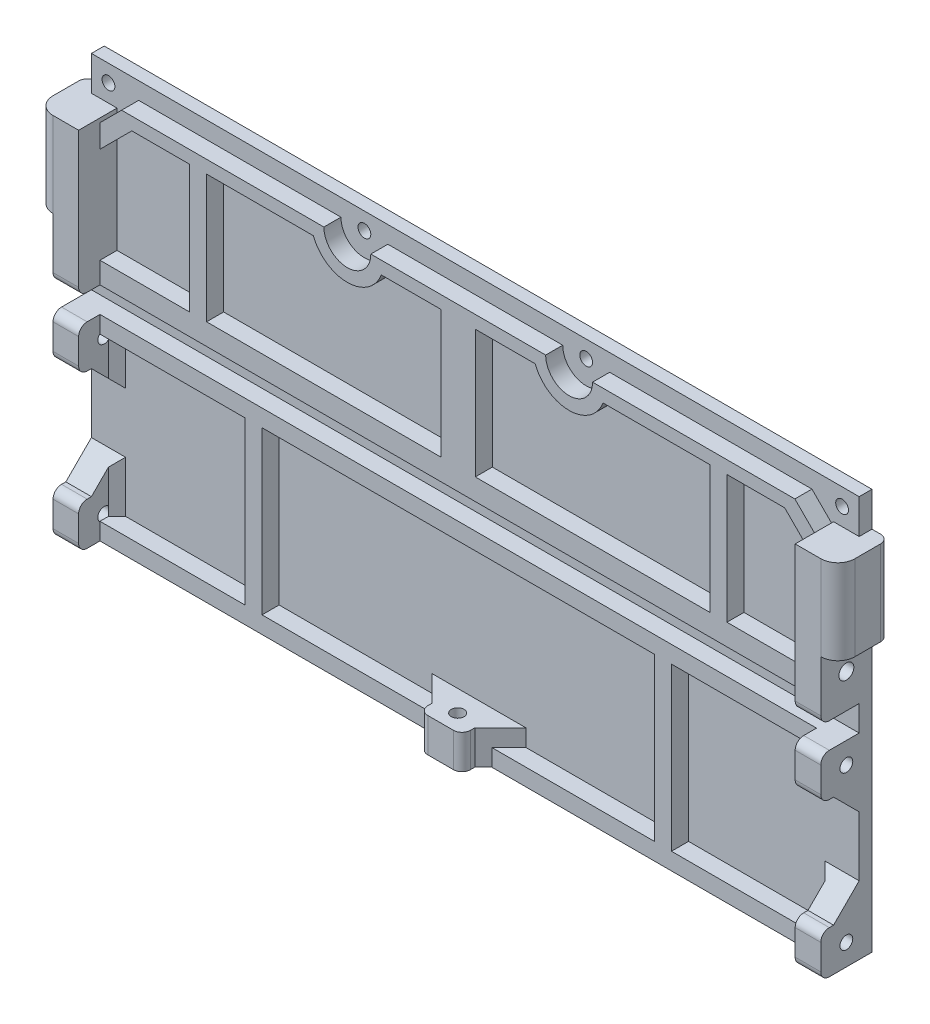
SolidWorks part; units mm, degrees
material "АБС-2020, черный"
ref_plane "Спереди" through (0, 0, 0) normal (0, 0, 1) x (1, 0, 0)
ref_plane "Сверху" through (0, 0, 0) normal (0, 1, 0) x (1, 0, 0)
ref_plane "Справа" through (0, 0, 0) normal (1, 0, 0) x (0, 0, -1)
other "Configuration Table"
sketch "Эскиз1" plane through (0, 0, 0) normal (0, 0, 1) x (1, 0, 0)
  line L1 (0, 0) -> (180, 0)
  line L2 (0, 0) -> (0, -94)
  line L3 (0, -94) -> (180, -94)
  line L4 (180, 0) -> (180, -94)
  dimension "D1" = 94
  dimension "D2" = 180
extrude "Бобышка-Вытянуть1" add sketch "Эскиз1" along normal blind 3
sketch "Эскиз2" plane through (0, 0, 3) normal (0, 0, 1) x (1, 0, 0)
  line L1 (0, -94) -> (6, -94)
  line L2 (0, -94) -> (0, -84)
  line L3 (0, -84) -> (6, -84)
  line L4 (6, -94) -> (6, -84)
  line L5 (180, -94) -> (174, -94)
  line L6 (180, -94) -> (180, -84)
  line L7 (180, -84) -> (174, -84)
  line L8 (174, -94) -> (174, -84)
  line L9 (0, -48) -> (6, -48)
  line L10 (0, -48) -> (0, -58)
  line L11 (0, -58) -> (6, -58)
  line L12 (6, -48) -> (6, -58)
  line L13 (180, -94) -> (180, 0) construction
  line L14 (180, -48) -> (174, -48)
  line L15 (180, -48) -> (180, -58)
  line L16 (180, -58) -> (174, -58)
  line L17 (174, -48) -> (174, -58)
  line L18 (0, -94) -> (180, -94) construction
  line L19 (180, 0) -> (0, 0) construction
  line L20 (180, -8.1) -> (174, -8.1)
  line L21 (180, -8.1) -> (180, -42)
  line L22 (180, -42) -> (174, -42)
  line L23 (174, -8.1) -> (174, -42)
  line L24 (0, -8.1) -> (6, -8.1)
  line L25 (0, -8.1) -> (0, -42)
  line L26 (0, -42) -> (6, -42)
  line L27 (6, -8.1) -> (6, -42)
  line L29 (85.876, -94) -> (95.876, -94)
  line L30 (85.876, -94) -> (85.876, -86)
  line L31 (85.876, -86) -> (95.876, -86)
  line L32 (95.876, -94) -> (95.876, -86)
  point P28 (3, -42)
  point P39 (0, 0)
  point P40 (90.876, -94)
  point P41 (0, 0)
  dimension "D1" = 10
  dimension "D2" = 6
  dimension "D3" = 10
  dimension "D4" = 6
  dimension "D5" = 46
  dimension "D6" = 6
  dimension "D7" = 6
  dimension "D9" = 10
  dimension "D10" = 10
  dimension "D11" = 6
  dimension "D12" = 8.1
  dimension "D13" = 8.1
  dimension "D14" = 6
  dimension "D15" = 10
  dimension "D16" = 5
  dimension "D17" = 8
extrude "Бобышка-Вытянуть2" add sketch "Эскиз2" along normal blind 9
chamfer "Фаска2" distance 6 angle 45 2 edges at (3, -58, 3) (177, -58, 3)
chamfer "Фаска1" distance 6 angle 45 2 edges at (3, -84, 3) (177, -84, 3)
sketch "Эскиз3" plane through (180, 0, 0) normal (1, 0, 0) x (0, 0, -1)
  line L0 (0, -94) -> (0, 0) construction
  line L1 (-12, -94) -> (0, -94) construction
  line L2 (-3, 0) -> (0, 0) construction
  circle A0 centre (-6, -89) radius 1.5
  circle A1 centre (-6, -53) radius 1.5
  circle A2 centre (-6, -34) radius 1.75
  dimension "D1" = 3
  dimension "D4" = 3
  dimension "D7" = 3.5
  dimension "D2" = 6
  dimension "D3" = 5
  dimension "D5" = 36
  dimension "D6" = 34
extrude "Вырез-Вытянуть1" cut sketch "Эскиз3" against normal blind 8
sketch "Эскиз4" plane through (0, 0, 3) normal (0, 0, 1) x (1, 0, 0)
  line L0 (0, -84) -> (0, -94) construction
  line L1 (180, -94) -> (180, -84) construction
  line L2 (180, 0) -> (0, 0) construction
  circle A0 centre (4, -4) radius 1.5
  circle A1 centre (176, -4) radius 1.5
  circle A2 centre (64, -4) radius 1.5
  circle A3 centre (116, -4) radius 1.5
  dimension "D7" = 3
  dimension "D4" = 3
  dimension "D5" = 3
  dimension "D1" = 4
  dimension "D2" = 4
  dimension "D3" = 4
  dimension "D6" = 60
  dimension "D8" = 60
extrude "Вырез-Вытянуть2" cut sketch "Эскиз4" against normal through all
sketch "Эскиз5" plane through (0, 0, 3) normal (0, 0, 1) x (1, 0, 0)
  line L2 (40, -52) -> (40, -90)
  line L4 (44, -52) -> (44, -90)
  line L5 (180, -78) -> (180, -64) construction
  line L7 (136, -52) -> (136, -90)
  line L9 (140, -52) -> (140, -90)
  line L10 (0, -64) -> (0, -78) construction
  line L11 (180, 0) -> (0, 0) construction
  line L13 (27, -4.5) -> (27, -37)
  line L15 (31, -4.5) -> (31, -37)
  line L18 (149, -4.5) -> (149, -37)
  line L20 (153, -4.5) -> (153, -37)
  line L21 (27, -4.5) -> (31, -4.5)
  line L22 (149, -4.5) -> (153, -4.5)
  line L23 (0, 0) -> (0, -8.1) construction
  line L24 (180, -48) -> (180, -42) construction
  line L25 (174, -8.1) -> (174, -42) construction
  line L26 (86, -4.5) -> (94, -4.5)
  line L27 (86, -4.5) -> (86, -37)
  line L29 (94, -4.5) -> (94, -37)
  line L31 (6, -42) -> (6, -37)
  line L32 (6, -37) -> (27, -37)
  line L33 (174, -42) -> (174, -37)
  line L34 (31, -37) -> (86, -37)
  line L35 (94, -37) -> (149, -37)
  line L36 (153, -37) -> (174, -37)
  line L37 (6, -42) -> (174, -42)
  line L39 (6, -48) -> (6, -52)
  line L40 (6, -52) -> (40, -52)
  line L41 (174, -48) -> (174, -52)
  line L42 (174, -48) -> (174, -58) construction
  line L43 (180, -48) -> (174, -48) construction
  line L44 (180, -48) -> (174, -48) construction
  line L45 (44, -52) -> (136, -52)
  line L46 (140, -52) -> (174, -52)
  line L47 (6, -48) -> (174, -48)
  line L48 (6, -90) -> (40, -90)
  line L49 (6, -94) -> (6, -84) construction
  line L50 (174, -84) -> (174, -94) construction
  line L51 (6, -90) -> (6, -94)
  line L53 (44, -90) -> (136, -90)
  line L54 (140, -90) -> (174, -90)
  line L55 (6, -94) -> (174, -94)
  line L56 (174, -94) -> (180, -94) construction
  line L57 (174, -94) -> (174, -90)
  point P5 (174, -94)
  dimension "D12" = 8
  dimension "D2" = 4
  dimension "D3" = 40
  dimension "D4" = 40
  dimension "D7" = 27
  dimension "D8" = 4
  dimension "D9" = 4.5
  dimension "D10" = 4
  dimension "D11" = 27
  dimension "D13" = 55
  dimension "D14" = 55
extrude "Бобышка-Вытянуть3" add sketch "Эскиз5" along normal blind 4
chamfer "Фаска3" distance 2 angle 45 4 edges at (174, -84, 3) (174, -58, 3) (6, -84, 3) (6, -58, 3)
sketch "Эскиз6" plane through (180, 0, 0) normal (1, 0, 0) x (0, 0, -1)
  line L0 (0, -94) -> (0, 0) construction
  line L1 (-12, -8.1) -> (0, -8.1)
  line L2 (-12, -8.1) -> (-12, -28)
  line L3 (-12, -28) -> (0, -28)
  line L4 (0, -8.1) -> (0, -28)
  line L5 (-3, 0) -> (0, 0) construction
  dimension "D1" = 28
  dimension "D2" = 8.1
extrude "Бобышка-Вытянуть4" add sketch "Эскиз6" along normal blind 4
fillet "Скругление1" radius 4 1 edges at (184, -18.05, 12)
sketch "Эскиз7" plane through (0, 0, 0) normal (-1, 0, 0) x (0, 0, 1)
  line L0 (12, -8.1) -> (12, -42) construction
  line L1 (0, -8.1) -> (12, -8.1)
  line L2 (0, -8.1) -> (0, -28)
  line L3 (0, -28) -> (12, -28)
  line L4 (12, -8.1) -> (12, -28)
  line L5 (3, 0) -> (0, 0) construction
  dimension "D1" = 28
extrude "Бобышка-Вытянуть5" add sketch "Эскиз7" along normal blind 4
fillet "Скругление2" radius 4 1 edges at (-4, -18.05, 12)
fillet "Скругление3" radius 2 2 edges at (184, -18.05, 0) (-4, -18.05, 0)
sketch "Эскиз8" plane through (0, -94, 0) normal (0, -1, 0) x (1, 0, 0)
  line L0 (95.876, 3) -> (136, 3) construction
  line L1 (85.876, 12) -> (85.876, 7) construction
  circle A0 centre (90.876, 8) radius 1.5
  dimension "D3" = 3
  dimension "D1" = 5
  dimension "D2" = 5
extrude "Вырез-Вытянуть3" cut sketch "Эскиз8" against normal blind 10
sketch "Эскиз9" plane through (0, 0, 0) normal (-1, 0, 0) x (0, 0, 1)
  line L0 (0, -28) -> (0, -94) construction
  line L1 (12, -94) -> (0, -94) construction
  circle A0 centre (6, -89) radius 1.5
  circle A1 centre (6, -53) radius 1.5
  point P8 (0, 0)
  dimension "D1" = 3
  dimension "D2" = 3
  dimension "D3" = 36
  dimension "D4" = 6
  dimension "D5" = 5
extrude "Вырез-Вытянуть4" cut sketch "Эскиз9" against normal blind 6
chamfer "Фаска4" distance 6 angle 45 2 edges at (95.876, -88, 3) (85.876, -88, 3)
fillet "Скругление4" radius 2 12 edges at (177, -84, 12) (3, -84, 12) (3, -42, 12) (3, -48, 12) (3, -58, 12) (3, -94, 12) (177, -42, 12) (177, -48, 12) (177, -58, 12) (85.876, -90, 12) (95.876, -90, 12) (177, -94, 12)
sketch "Эскиз10" plane through (0, 0, 3) normal (0, 0, 1) x (1, 0, 0)
  line L0 (11.0731, -4) -> (58.5, -4)
  line L1 (6, -14.4642) -> (13.4642, -7)
  line L2 (6, -37) -> (6, -8.1) construction
  line L3 (13.4642, -7) -> (56.047, -7)
  line L4 (166.5358, -7) -> (174, -14.4642)
  line L5 (174, -8.1) -> (174, -40) construction
  line L6 (174, -14.4642) -> (174, -9.0731)
  line L7 (174, -8.1) -> (174, -37) construction
  line L9 (174, -9.0731) -> (168.9269, -4)
  line L10 (6, -9.0731) -> (11.0731, -4)
  line L11 (69.5, -4) -> (110.5, -4)
  line L12 (71.953, -7) -> (108.047, -7)
  line L13 (6, -40) -> (6, -8.1) construction
  line L14 (123.953, -7) -> (166.5358, -7)
  line L15 (121.5, -4) -> (168.9269, -4)
  line L16 (6, -9.0731) -> (6, -14.4642)
  arc A0 (110.5, -4) -> (121.5, -4) centre (116, -4) ccw
  arc A1 (58.5, -4) -> (69.5, -4) centre (64, -4) ccw
  arc A4 (56.047, -7) -> (71.953, -7) centre (64, -4) ccw
  arc A5 (108.047, -7) -> (123.953, -7) centre (116, -4) ccw
  point P1 (6, -8.1)
  point P12 (6, -9.0731)
  point P26 (174, -9.0731)
  point P35 (0, 0)
  point P36 (0, 0)
  line M8 (6, -8.1) -> (6, -37)
  line M10 (27, -37) -> (27, -4.5)
  line M11 (27, -4.5) -> (31, -4.5)
  line M12 (31, -4.5) -> (31, -37)
  line M14 (86, -37) -> (86, -4.5)
  line M15 (86, -4.5) -> (94, -4.5)
  line M16 (94, -4.5) -> (94, -37)
  line M18 (149, -37) -> (149, -4.5)
  line M19 (149, -4.5) -> (153, -4.5)
  line M20 (153, -4.5) -> (153, -37)
  line M22 (174, -37) -> (174, -8.1)
  dimension "D1" = 17
  dimension "D5" = 17
  dimension "D2" = 3
  dimension "D3" = 45
  dimension "D4" = 45
extrude "Бобышка-Вытянуть6" add sketch "Эскиз10" along normal blind 4 contours L12 A5 L15 A0 L11 A1 L0 L10 L1 L3 A4 M8 M10 M11 M12 M14 M15 M16 | A5 L14 L4 L9 L15 M18 M19 M20 M22 region at (34.7866, -5.6833, 3)
